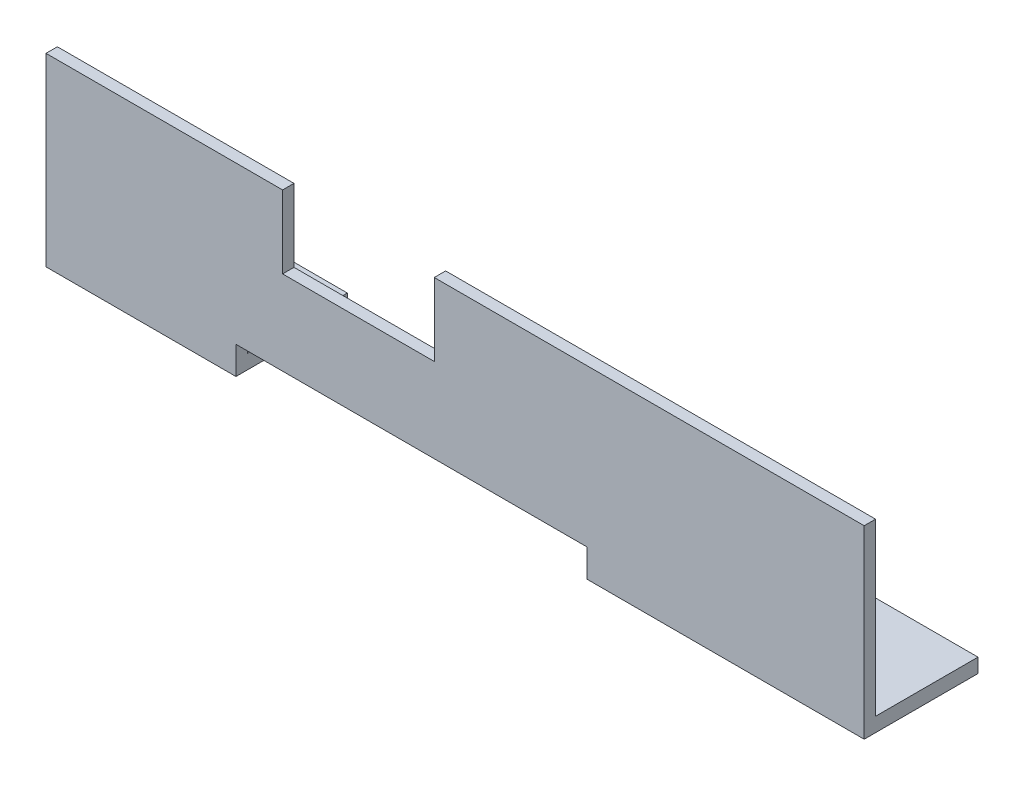
SolidWorks part; units mm, degrees
ref_plane "Спереди" through (0, 0, 0) normal (0, 0, 1) x (1, 0, 0)
ref_plane "Сверху" through (0, 0, 0) normal (0, 1, 0) x (1, 0, 0)
ref_plane "Справа" through (0, 0, 0) normal (1, 0, 0) x (0, 0, -1)
sketch "Эскиз1" plane through (0, 0, 0) normal (1, 0, 0) x (0, 0, -1)
  line L0 (0, 0) -> (0, 60)
  line L1 (0, 0) -> (36, 0)
  line L2 (36, 0) -> (36, -5)
  line L3 (36, -5) -> (-4, -5)
  line L4 (-4, -5) -> (-4, 60)
  line L5 (-4, 60) -> (0, 60)
extrude "Вытянуть1" add sketch "Эскиз1" along normal up to surface (287.5765 mm away)
sketch "Эскиз2" plane through (0, 0, -36) normal (0, 0, -1) x (-1, 0, 0)
  line L1 (-190.2228, 4.8196) -> (-66.7627, 4.8196)
  line L2 (-190.2228, 4.8196) -> (-190.2228, -10.755)
  line L3 (-190.2228, -10.755) -> (-66.7627, -10.755)
  line L4 (-66.7627, 4.8196) -> (-66.7627, -10.755)
extrude "Вырез-Вытянуть1" cut sketch "Эскиз2" against normal through all from offset 20 offset against normal yes
sketch "Эскиз3" plane through (0, 0, 0) normal (0, 0, -1) x (-1, 0, 0)
  line L1 (-136.4668, 64.4868) -> (-83.1623, 64.4868)
  line L2 (-136.4668, 64.4868) -> (-136.4668, 34.4358)
  line L3 (-136.4668, 34.4358) -> (-83.1623, 34.4358)
  line L4 (-83.1623, 64.4868) -> (-83.1623, 34.4358)
extrude "Вырез-Вытянуть2" cut sketch "Эскиз3" against normal blind 40
sketch "Эскиз4" plane through (0, 0, 0) normal (0, 1, 0) x (1, 0, 0)
  line L1 (65.9253, 36.8821) -> (154.5046, 36.8821)
  line L2 (65.9253, 36.8821) -> (65.9253, 29.8998)
  line L3 (65.9253, 29.8998) -> (154.5046, 29.8998)
  line L4 (154.5046, 36.8821) -> (154.5046, 29.8998)
extrude "Вырез-Вытянуть3" cut sketch "Эскиз4" against normal through all
